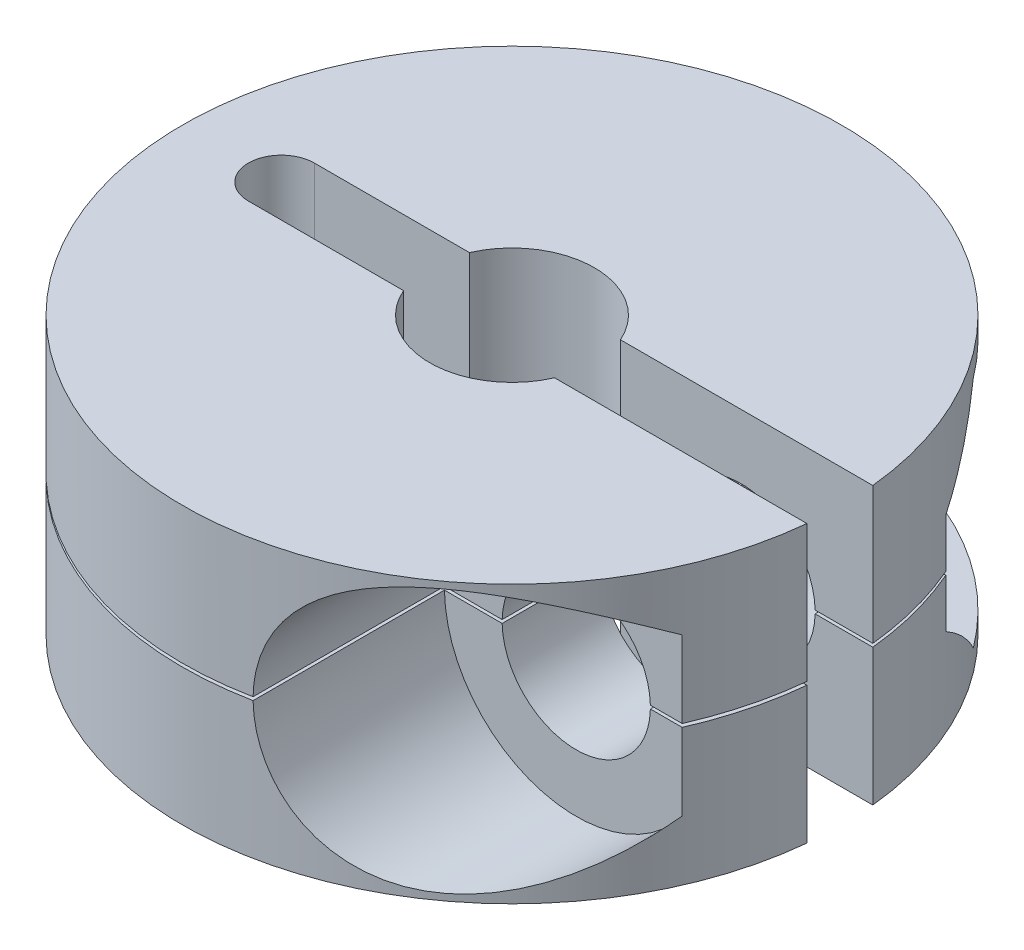
SolidWorks part; units mm, degrees
ref_plane "Front Plane" through (0, 0, 0) normal (0, 0, 1) x (1, 0, 0)
ref_plane "Top Plane" through (0, 0, 0) normal (0, 1, 0) x (1, 0, 0)
ref_plane "Right Plane" through (0, 0, 0) normal (1, 0, 0) x (0, 0, -1)
sketch "Sketch1" plane through (0, 0, 0) normal (0, 1, 0) x (1, 0, 0)
  circle A0 centre (0, 0) radius 10
  circle A1 centre (0, 0) radius 2.5
  dimension "D1" = 5
  dimension "D2" = 20
extrude "Boss-Extrude1" add sketch "Sketch1" along normal mid plane 8.4
sketch "Sketch2" plane through (0, 4.2, 0) normal (0, 1, 0) x (1, 0, 0)
  line L0 (-7, 0) -> (9.9499, 0) construction
  line L1 (-7, 1) -> (9.9499, 1)
  line L2 (-7, -1) -> (9.9499, -1)
  line L3 (-7.4844, 6.632) -> (-3.3518, 11.2958) construction
  line L6 (0, -10) -> (4.2019, -10) construction
  line L7 (0, -10) -> (0, -12.2865) construction
  line L8 (-7.4844, 6.632) -> (-9.1052, 8.0682) construction
  arc A0 (-7, 1) -> (-7, -1) centre (-7, 0) ccw
  arc A1 (9.9499, -1) -> (9.9499, 1) centre (9.9499, 0) ccw
  arc A2 (-7.4844, 6.632) -> (0, -10) centre (0, 0) ccw construction
  circle A4 centre (0, 0) radius 10 construction
  circle A5 centre (0, 0) radius 2.5 construction
  arc A8 (-4.5, 0) -> (-2.9844, -3.368) centre (0, 0) ccw construction
  arc A9 (-7.4844, 6.632) -> (-4.5, 0) centre (-13.3611, 0) cw construction
  arc A10 (-2.9844, -3.368) -> (0, -10) centre (-8.8611, -10) cw construction
  point P2 (1.4749, 0)
  dimension "D1" = 1
  dimension "D2" = 7
  dimension "D3" = 2
extrude "Cut-Extrude1" cut sketch "Sketch2" against normal through all
sketch "Sketch3" plane through (0, 0, -1) normal (0, 0, 1) x (1, 0, 0)
  line L0 (5.9499, 0) -> (9.9499, 0) construction
  line L1 (9.9499, 4.2) -> (9.9499, -4.2) construction
  circle A0 centre (5.9499, 0) radius 2.25
  dimension "D1" = 4.5
  dimension "D2" = 4
extrude "Cut-Extrude2" cut sketch "Sketch3" against normal blind 10 and the other way through all
sketch "Sketch4" plane through (0, 0, 1) normal (0, 0, -1) x (-1, 0, 0)
  line L1 (-1.8507, 0) -> (-3.9003, 3.55)
  line L2 (-3.9003, 3.55) -> (-7.9995, 3.55)
  line L3 (-7.9995, 3.55) -> (-10.0491, 0)
  line L4 (-10.0491, 0) -> (-7.9995, -3.55)
  line L5 (-7.9995, -3.55) -> (-3.9003, -3.55)
  line L6 (-3.9003, -3.55) -> (-1.8507, 0)
  circle A0 centre (-5.9499, 0) radius 3.55 construction
  dimension "D1" = 7.1
extrude "Cut-Extrude3" cut sketch "Sketch4" along normal blind 10 from offset 5
sketch "Sketch6" plane through (0, 0, -1) normal (0, 0, 1) x (1, 0, 0)
  circle A0 centre (5.9499, 0) radius 4
  dimension "D1" = 8
extrude "Cut-Extrude4" cut sketch "Sketch6" along normal blind 10 from offset 5
sketch "Sketch9" plane through (0, 0, 0) normal (0, 1, 0) x (1, 0, 0)
  circle A0 centre (0, 0) radius 10
  arc A1 (9.9499, 1) -> (9.9499, -1) centre (0, 0) ccw construction
extrude "Cut-Extrude5" cut sketch "Sketch9" against normal mid plane 0.1
